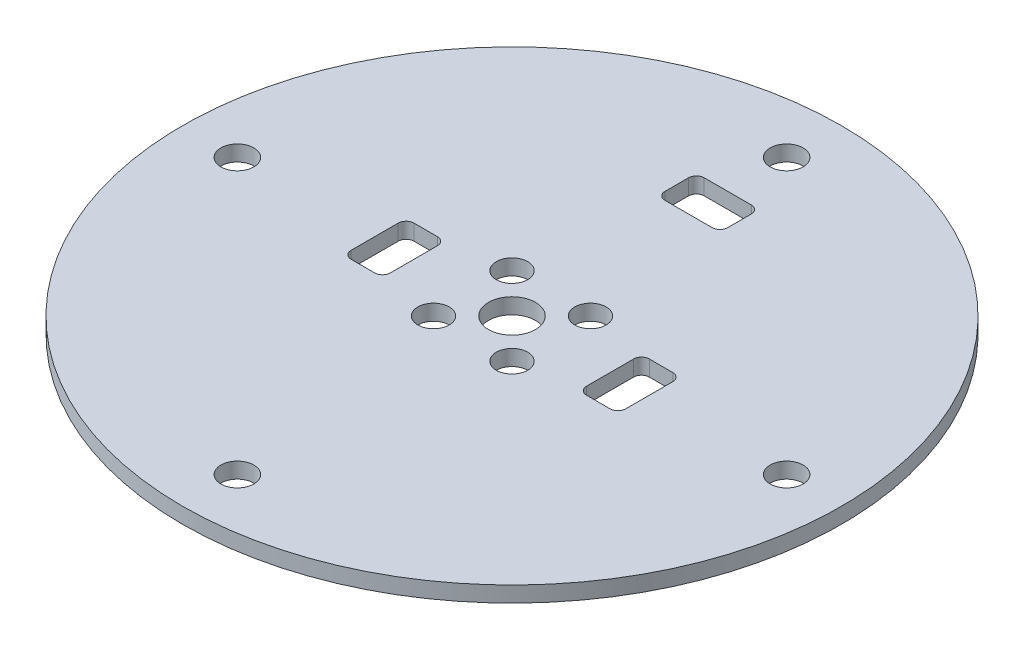
SolidWorks part; units mm, degrees
note: The reader was unsure of these and kept them because the rebuilt part matched: thickness of "基体-法兰1", "钣金6", "钣金7".
ref_plane "前视基准面" through (0, 0, 0) normal (0, 0, 1) x (1, 0, 0)
ref_plane "上视基准面" through (0, 0, 0) normal (0, 1, 0) x (1, 0, 0)
ref_plane "右视基准面" through (0, 0, 0) normal (1, 0, 0) x (0, 0, -1)
sketch "草图1" plane through (0, 0, 0) normal (0, 1, 0) x (1, 0, 0)
  circle A0 centre (0, 0) radius 42
  dimension "D1" = 84
base flange "基体-法兰1" sketch "草图1" thickness 2 reverse thickness direction no parameters "D1"=0.7366
sketch "草图6" plane through (0, 0, 0) normal (0, 1, 0) x (1, 0, 0)
  line L0 (0, 42) -> (0, -42) construction
  line L1 (-42, 0) -> (42, 0) construction
  line L3 (4, 22.5) -> (-4, 22.5)
  line L4 (4, 22.5) -> (4, 27.5)
  line L5 (4, 27.5) -> (-4, 27.5)
  line L6 (-4, 22.5) -> (-4, 27.5)
  line L7 (4, 22.5) -> (-4, 27.5) construction
  line L8 (4, 27.5) -> (-4, 22.5) construction
  line L22 (17.5, 4) -> (12.5, 4)
  line L23 (-17.5, -4) -> (-12.5, -4)
  line L24 (-17.5, -4) -> (-17.5, 4)
  line L25 (-17.5, 4) -> (-12.5, 4)
  line L26 (-12.5, -4) -> (-12.5, 4)
  line L27 (-17.5, -4) -> (-12.5, 4) construction
  line L28 (-17.5, 4) -> (-12.5, -4) construction
  line L29 (12.5, -4) -> (12.5, 4)
  line L30 (17.5, -4) -> (12.5, -4)
  line L31 (17.5, -4) -> (17.5, 4)
  circle A0 centre (0, 0) radius 42 construction
  circle A1 centre (0, 35) radius 2.1
  circle A2 centre (35, 0) radius 2.1
  circle A3 centre (0, -35) radius 2.1
  circle A4 centre (-35, 0) radius 2.1
  circle A5 centre (0, 0) radius 3
  circle A11 centre (-5, 5) radius 2
  circle A12 centre (5, 5) radius 2
  circle A13 centre (5, -5) radius 2
  circle A14 centre (-5, -5) radius 2
  point P12 (0, 25)
  point P19 (0, 0)
  point P24 (0, 0)
  point P25 (0, 0)
  point P32 (-15, 0)
  dimension "D1" = 4.2
  dimension "D4" = 6
  dimension "D13" = 5
  dimension "D14" = 2
  dimension "D10" = 4
  dimension "D2" = 35
  dimension "D5" = 5
  dimension "D6" = 8
  dimension "D8" = 15
  dimension "D11" = 25
  dimension "D12" = 5
  dimension "D15" = 2
  dimension "D18" = 8
  dimension "D19" = 5
  dimension "D3" = 4
extrude "切除-拉伸1" cut sketch "草图6" against normal up to next normal cut yes
fillet "圆角1" radius 1 12 edges at (4, -1, -22.5) (4, -1, -27.5) (-4, -1, -27.5) (-4, -1, -22.5) (-12.5, -1, -4) (-17.5, -1, -4) (-12.5, -1, 4) (-17.5, -1, 4) (17.5, -1, 4) (12.5, -1, 4) (12.5, -1, -4) (17.5, -1, -4)
sketch "折弯-线1" plane through (0, 0, 0) normal (0, 1, 0) x (1, 0, 0)
sketch "边界框1" plane through (0, 0, 0) normal (0, 1, 0) x (1, 0, 0)
sheet metal parameters "钣金6" thickness 2 parameters "D1"=0.7366
flat pattern "平板型式6" [suppressed]
sketch "折弯-线2" plane through (0, 0, 0) normal (0, 1, 0) x (1, 0, 0)
sketch "边界框2" [suppressed] plane through (0, 0, 0) normal (0, 1, 0) x (1, 0, 0)
sheet metal parameters "钣金7" thickness 2 parameters "D1"=0.7366, "D7"=3
flat pattern "平板型式6"
sketch "折弯-线2" plane through (0, 0, 0) normal (0, 1, 0) x (1, 0, 0)
sketch "边界框2" [suppressed] plane through (0, 0, 0) normal (0, 1, 0) x (1, 0, 0)
